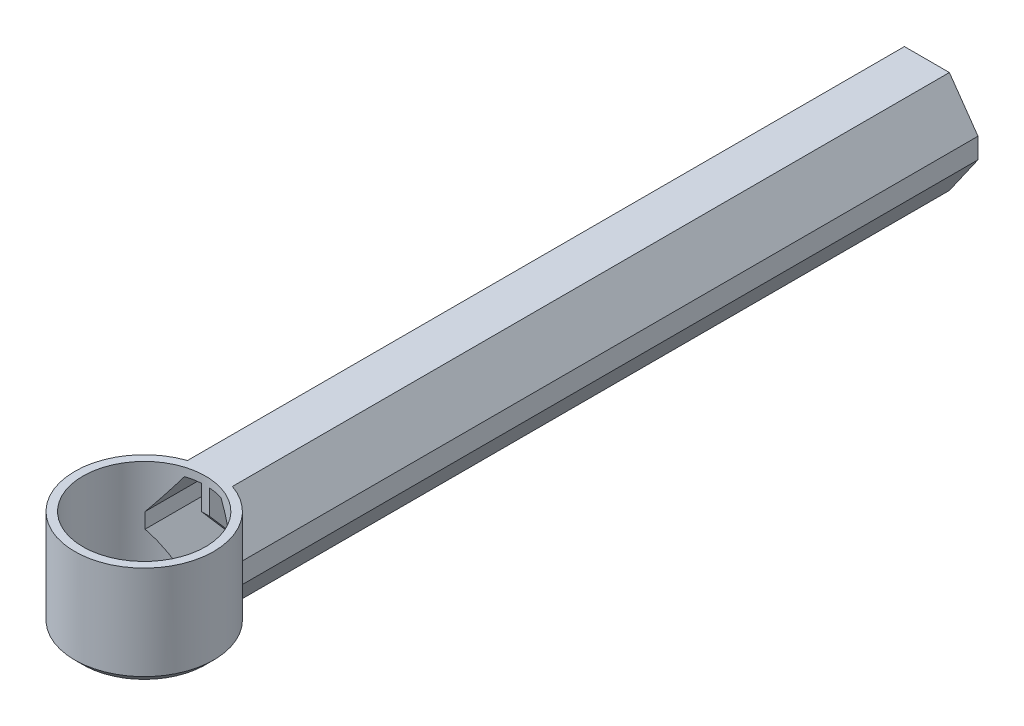
SolidWorks part; units mm, degrees
ref_plane "Piano frontale" through (0, 0, 0) normal (0, 0, 1) x (1, 0, 0)
ref_plane "Piano superiore" through (0, 0, 0) normal (0, 1, 0) x (1, 0, 0)
ref_plane "Piano destro" through (0, 0, 0) normal (1, 0, 0) x (0, 0, -1)
sketch "Schizzo1" plane through (0, 0, 0) normal (0, 0, 1) x (1, 0, 0)
  line L0 (3.6233, 15.123) -> (10.6233, 5.123)
  line L1 (-7.3767, 15.123) -> (3.6233, 15.123)
  line L2 (-7.3767, 15.123) -> (-7.3767, -9.877) construction
  line L3 (-7.3767, -9.877) -> (3.6233, -9.877)
  line L4 (-7.3767, -9.877) -> (-7.3597, -9.8281)
  line L5 (-6.3354, 13.123) -> (-12.3767, 4.4925)
  line L6 (-14.3767, 5.123) -> (-14.3767, 0.123)
  line L7 (-6.3354, 13.123) -> (2.582, 13.123)
  line L8 (10.6233, 5.123) -> (10.6233, 0.123)
  line L9 (10.6233, 0.123) -> (3.6233, -9.877)
  line L10 (-7.3767, -9.877) -> (-14.3767, 0.123)
  line L11 (-14.3767, 5.123) -> (-7.3767, 15.123)
  line L12 (-14.3767, 0.123) -> (10.6233, 0.123) construction
  line L13 (-6.3354, -7.877) -> (2.582, -7.877)
  line L15 (-2.8767, 13.123) -> (-0.8767, 13.123)
  line L16 (-12.3767, 4.4925) -> (-12.3767, 0.7534)
  line L17 (-2.8767, 13.123) -> (-2.8767, -7.877)
  line L18 (8.6233, 4.4925) -> (8.6233, 0.7534)
  line L19 (-12.3767, 0.7534) -> (-6.3354, -7.877)
  line L20 (2.582, -7.877) -> (8.6233, 0.7534)
  line L21 (8.6233, 4.4925) -> (2.582, 13.123)
  line L22 (-2.8767, -7.877) -> (-0.8767, -7.877)
  line L23 (-0.8767, 13.123) -> (-0.8767, -7.877)
  dimension "D1" = 11
  dimension "D2" = 5
  dimension "D3" = 25
  dimension "D4" = 25
  dimension "D5" = 2
  dimension "D6" = 2
  dimension "D7" = 2
  dimension "D8" = 2
  dimension "D9" = 2
  dimension "D10" = 2
  dimension "D11" = 9.5
extrude "Estrusione-Estrusione1" add sketch "Schizzo1" along normal blind 180 contours L11 L6 L10 L3 L9 L8 L0 L1 L21 L18 L20 L13 L19 L16 L5 L7 | L23 L7 L17 L13 region at (6.8336, 9.9202, 0) region at (-1.8767, 2.623, 0)
sketch "Schizzo3" plane through (0, 15.123, 0) normal (0, 1, 0) x (1, 0, 0)
  circle A0 centre (-1.8767, -191.5217) radius 17
  dimension "D1" = 34
extrude "Taglio-Estrusione2" cut sketch "Schizzo3" against normal through all
sketch "Schizzo4" plane through (0, 15.123, 0) normal (0, 1, 0) x (1, 0, 0)
  circle A0 centre (-1.8767, -191.5217) radius 17 construction
  arc A1 (3.6233, -175.436) -> (-7.3767, -175.436) centre (-1.8767, -191.5217) ccw construction
  arc A2 (-7.3767, -175.436) -> (3.6233, -175.436) centre (-1.8767, -191.5217) ccw
  circle A3 centre (-1.8767, -191.5217) radius 15 construction
  circle A4 centre (-1.8767, -191.5217) radius 15
  arc M5 (-7.3767, -175.436) -> (3.6233, -175.436) centre (-1.8767, -191.5217) cw
  dimension "D1" = 34
  dimension "D2" = 30
extrude "Estrusione-Estrusione2" add sketch "Schizzo4" against normal through all contours A2 A4 M5 region at (-1.8767, 15.123, 175.0026)
sketch "Schizzo6" plane through (0, -9.877, 0) normal (0, -1, 0) x (1, 0, 0)
  circle A0 centre (-1.8767, 191.5217) radius 15
extrude "Estrusione-Estrusione3" add sketch "Schizzo6" against normal blind 2
sketch "Schizzo8" plane through (0, 0, 0) normal (0, 0, -1) x (-1, 0, 0)
  line L0 (0.8767, -7.877) -> (-2.582, -7.877)
  line L1 (-2.582, -7.877) -> (-8.6233, 0.7534)
  line L2 (-8.6233, 0.7534) -> (-8.6233, 4.4925)
  line L3 (-8.6233, 4.4925) -> (-2.582, 13.123)
  line L4 (-2.582, 13.123) -> (0.8767, 13.123)
  line L5 (0.8767, 13.123) -> (0.8767, -7.877)
  line L6 (2.8767, -7.877) -> (2.8767, 13.123)
  line L7 (2.8767, 13.123) -> (6.3354, 13.123)
  line L8 (6.3354, 13.123) -> (12.3767, 4.4925)
  line L9 (12.3767, 4.4925) -> (12.3767, 0.7534)
  line L10 (12.3767, 0.7534) -> (6.3354, -7.877)
  line L11 (6.3354, -7.877) -> (2.8767, -7.877)
extrude "Taglio-Estrusione4" cut sketch "Schizzo8" against normal up to next
sketch "Schizzo10" plane through (-0.8767, 0, 0) normal (1, 0, 0) x (0, 0, -1)
  line L0 (-176.5551, -7.877) -> (-176.5551, 7.123)
  line L1 (-176.5551, 7.123) -> (-163.5551, -7.877)
  line L2 (-176.5551, -7.877) -> (0, -7.877) construction
  line L3 (-163.5551, -7.877) -> (-176.5551, -7.877)
  line L4 (-176.5551, 13.123) -> (-176.5551, -7.877) construction
  dimension "D1" = 6
  dimension "D2" = 13
extrude "Taglio-Estrusione5" cut sketch "Schizzo10" against normal up to next
sketch "Schizzo11" plane through (0, -7.877, 0) normal (0, 1, 0) x (1, 0, 0)
  circle A0 centre (-1.8767, -191.5217) radius 15
extrude "Estrusione-Estrusione4" add sketch "Schizzo11" along normal blind 1
chamfer "Smusso1" distance 2 angle 30 1 edges at (-1.8767, -7.877, 176.5217) first distance on face at (-1.8767, -7.877, 85.104)
chamfer "Smusso2" distance 2 angle 45 1 edges at (-1.8767, -9.877, 208.5217)
sketch "Schizzo12" plane through (0, -6.877, 0) normal (0, 1, 0) x (1, 0, 0)
  circle A0 centre (-1.8767, -191.5217) radius 2.5
  dimension "D1" = 5
extrude "Taglio-Estrusione6" cut sketch "Schizzo12" against normal through all
sketch "Schizzo13" plane through (0, -6.877, 0) normal (0, 1, 0) x (1, 0, 0)
  circle A0 centre (-1.8767, -191.5217) radius 4.75
  circle A1 centre (-1.8767, -191.5217) radius 2.5 construction
  dimension "D1" = 9.5
extrude "Taglio-Estrusione7" cut sketch "Schizzo13" against normal blind 2
sketch "Schizzo14" plane through (0, -6.877, 0) normal (0, 1, 0) x (1, 0, 0)
  circle A0 centre (-7.5233, -197.1888) radius 1.2295 construction
  circle A1 centre (4.853, -198.227) radius 1.2295 construction
  circle A2 centre (3.7698, -185.8546) radius 1.2295 construction
  circle A3 centre (-8.6064, -184.8164) radius 1.2295 construction
  circle A7 centre (4.853, -198.227) radius 1.5
  circle A16 centre (-8.6064, -184.8164) radius 1.5
  circle A17 centre (-8.6064, -184.8164) radius 1.5
  circle A18 centre (-7.5233, -197.1888) radius 1.5
  circle A19 centre (3.7698, -185.8546) radius 1.5
  point P56 (-15.9445, -181.5343)
  point P73 (-1.8767, -191.5217)
  point P106 (-15.9445, -181.5343)
  dimension "D3" = 2
  dimension "D5" = 3
extrude "Taglio-Estrusione9" cut sketch "Schizzo14" against normal through all contours A16 | A19 | A7 | A18
